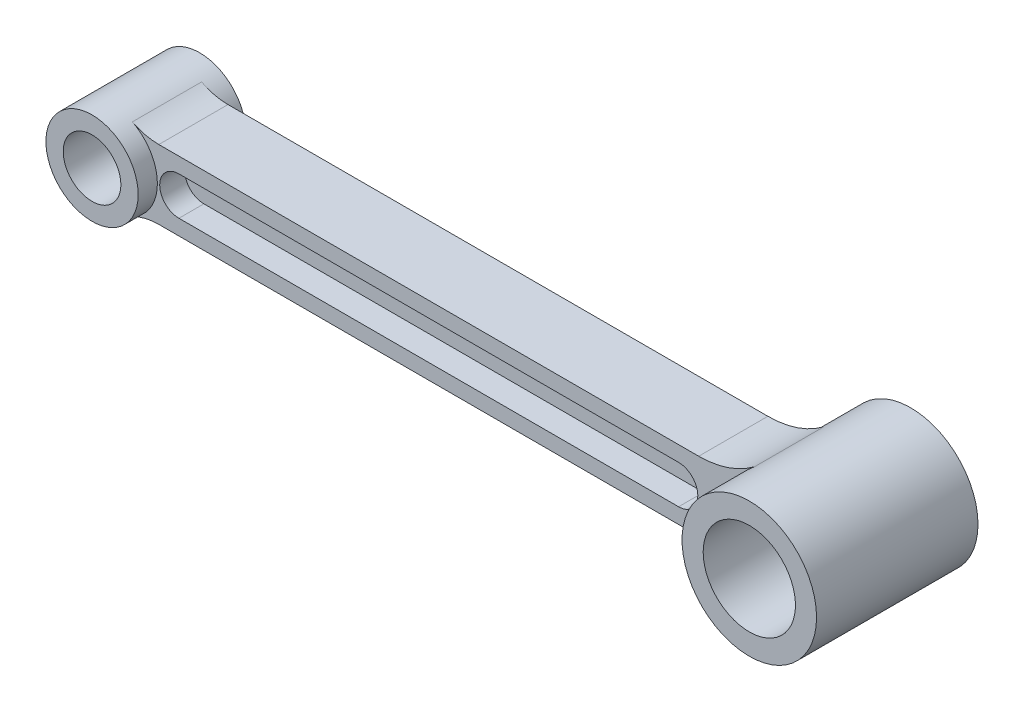
SolidWorks part; units mm, degrees
ref_plane "Front Plane" through (0, 0, 0) normal (0, 0, 1) x (1, 0, 0)
ref_plane "Top Plane" through (0, 0, 0) normal (0, 1, 0) x (1, 0, 0)
ref_plane "Right Plane" through (0, 0, 0) normal (1, 0, 0) x (0, 0, -1)
sketch "Sketch1" plane through (0, 0, 0) normal (0, 0, 1) x (1, 0, 0)
  line L0 (-46.1088, 0) -> (131.8912, 0) construction
  line L1 (-33.7394, 9) -> (106.7268, 9)
  line L2 (-33.7394, -9) -> (106.7268, -9)
  circle A0 centre (-46.1088, 0) radius 12
  circle A1 centre (-46.1088, 0) radius 7.5
  circle A2 centre (131.8912, 0) radius 17.5
  circle A3 centre (131.8912, 0) radius 12
  arc A4 (-40.6113, 10.6667) -> (-33.7394, 9) centre (-33.7394, 24) ccw
  arc A5 (121.2797, 13.9157) -> (106.7268, 9) centre (106.7268, 33) cw
  arc A6 (121.2797, -13.9157) -> (106.7268, -9) centre (106.7268, -33) ccw
  arc A7 (-40.6113, -10.6667) -> (-33.7394, -9) centre (-33.7394, -24) cw
  dimension "D1" = 15
  dimension "D2" = 24
  dimension "D3" = 35
  dimension "D4" = 24
  dimension "D6" = 15
  dimension "D7" = 24
  dimension "D5" = 178
  dimension "D8" = 9
extrude "Boss-Extrude2" add sketch "Sketch1" along normal mid plane 28 contours A1 A0 region at (-36.1524, 6.0695, 0)
extrude "Boss-Extrude3" add sketch "Sketch1<7>" along normal mid plane 42 separate body contours A2 | A3
sketch "Sketch1<7>" plane through (0, 0, 0) normal (0, 0, 1) x (1, 0, 0) same geometry as "Sketch1"
extrude "Boss-Extrude4" add sketch "Sketch1<11>" along normal mid plane 18 contours A0 L0 A2 A5 L1 A4 | L0 A0 A7 L2 A6 A2 region at (40.4164, 4.5801, 0) region at (40.4164, -4.5801, 0)
sketch "Sketch1<11>" plane through (0, 0, 0) normal (0, 0, 1) x (1, 0, 0) same geometry as "Sketch1"
ref_plane "Plane2" through (0, 0, 0) normal (0, 0, -1) x (-1, 0, 0)
sketch "Sketch2" plane through (0, 0, 0) normal (0, 0, -1) x (-1, 0, 0)
  line L0 (-131.8912, 0) -> (78.6374, 0) construction
  line L1 (-101.4937, 0) -> (28.5063, 0) construction
  line L2 (-101.4937, 5) -> (28.5063, 5)
  line L3 (-101.4937, -5) -> (28.5063, -5)
  line L4 (33.7394, 9) -> (-106.7268, 9) construction
  arc A0 (-101.4937, 5) -> (-101.4937, -5) centre (-101.4937, 0) ccw
  arc A1 (28.5063, -5) -> (28.5063, 5) centre (28.5063, 0) ccw
  point P6 (-36.4937, 0)
  point P15 (-36.4937, 9)
  dimension "D2" = 5
  dimension "D1" = 130
extrude "Cut-Extrude1" cut sketch "Sketch2" along normal blind 18 from offset 2.5
mirror "Mirror1" about plane through (0, 0, 0) normal (0, 0, -1) of "Cut-Extrude1"
